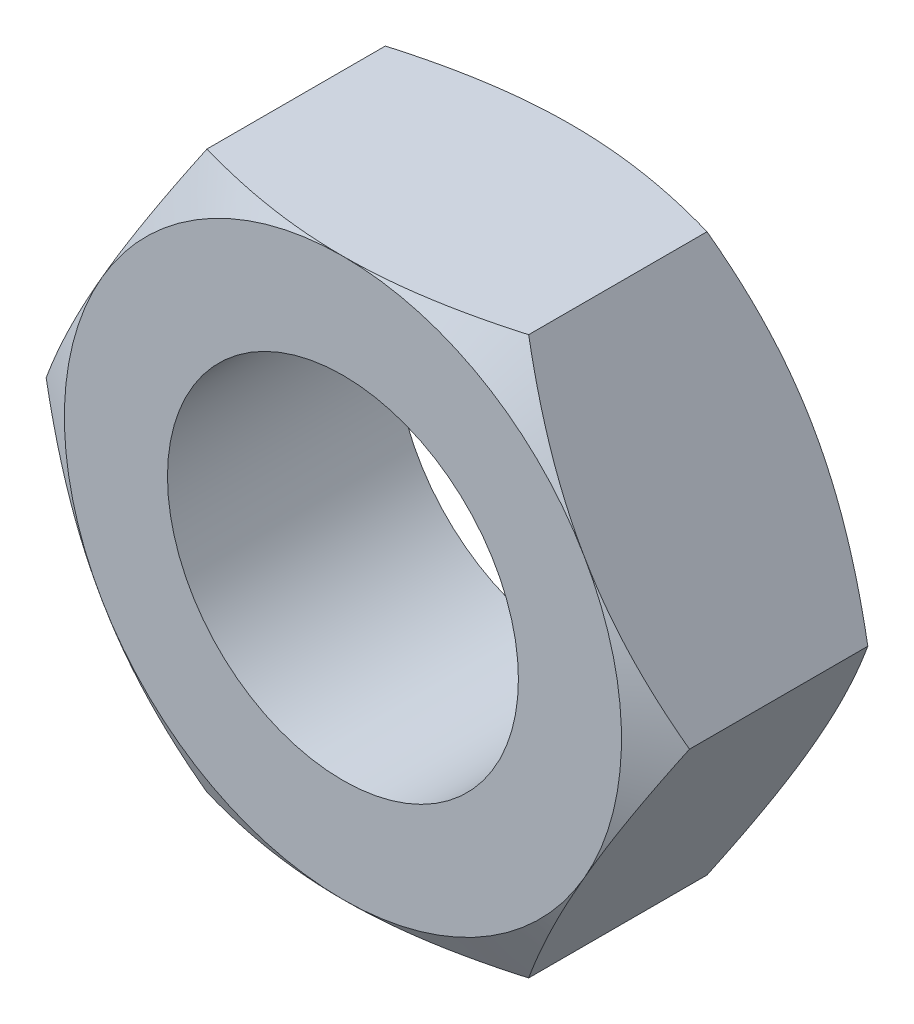
SolidWorks part; units mm, degrees
ref_plane "Front Plane" through (0, 0, 0) normal (0, 0, 1) x (1, 0, 0)
ref_plane "Top Plane" through (0, 0, 0) normal (0, 1, 0) x (1, 0, 0)
ref_plane "Right Plane" through (0, 0, 0) normal (1, 0, 0) x (0, 0, -1)
sketch "Sketch1" plane through (0, 0, 0) normal (0, 0, 1) x (1, 0, 0)
  line L1 (7.3323, 0) -> (3.6662, 6.35)
  line L2 (3.6662, 6.35) -> (-3.6662, 6.35)
  line L3 (-3.6662, 6.35) -> (-7.3323, 0)
  line L4 (-7.3323, 0) -> (-3.6662, -6.35)
  line L5 (-3.6662, -6.35) -> (3.6662, -6.35)
  line L6 (3.6662, -6.35) -> (7.3323, 0)
  circle A0 centre (0, 0) radius 4
  circle A1 centre (0, 0) radius 6.35 construction
  dimension "D1" = 8
  dimension "D2" = 12.7
extrude "Boss-Extrude1" add sketch "Sketch1" along normal blind 5.2
ref_axis "Axis1" through (0, 0, 13.1472) along (0, 0, -1)
sketch "Sketch2" plane through (0, 0, 5.2) normal (0, 0, 1) x (1, 0, 0)
  circle A0 centre (0, 0) radius 6.35
extrude "Cut-Extrude1" cut sketch "Sketch2" against normal blind 5 draft 60 flip side to cut
sketch "Sketch3" plane through (0, 0, 0) normal (0, 0, -1) x (-1, 0, 0)
  circle A0 centre (0, 0) radius 6.35
extrude "Cut-Extrude2" cut sketch "Sketch3" against normal blind 5 draft 60 flip side to cut
